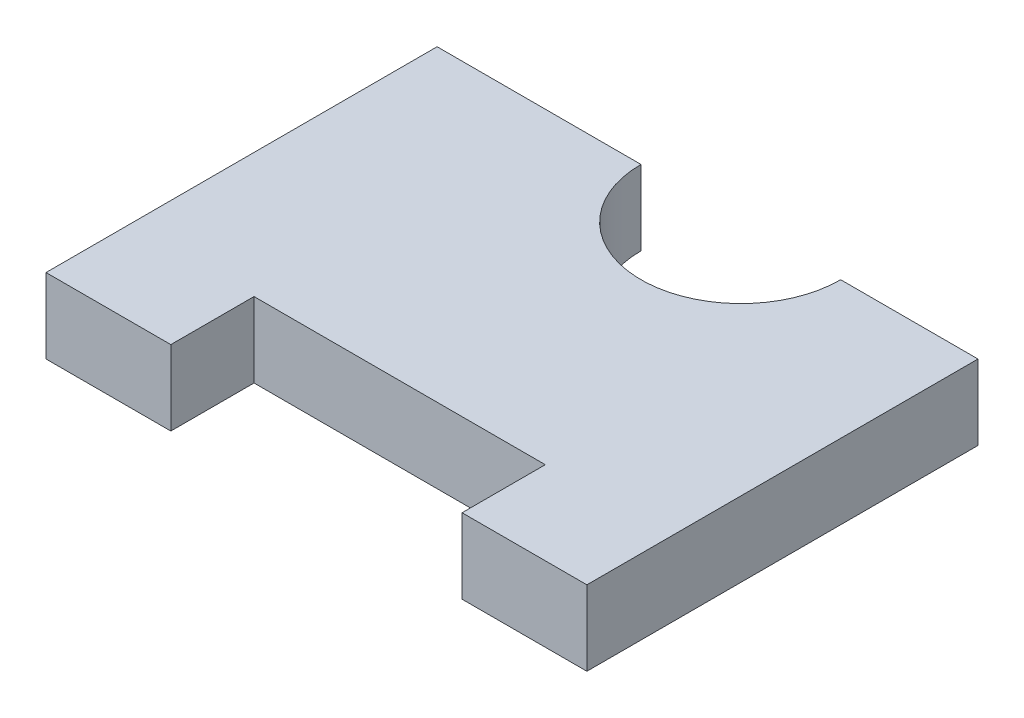
SolidWorks part; units mm, degrees
ref_plane "Front Plane" through (0, 0, 0) normal (0, 0, 1) x (1, 0, 0)
ref_plane "Top Plane" through (0, 0, 0) normal (0, 1, 0) x (1, 0, 0)
ref_plane "Right Plane" through (0, 0, 0) normal (1, 0, 0) x (0, 0, -1)
sketch "Sketch1" plane through (0, 0, 0) normal (0, 1, 0) x (1, 0, 0)
  line L0 (6.5, 5) -> (6.5, 0)
  line L1 (3.5, 0) -> (-3.5, 0)
  line L2 (-6.5, 0) -> (-6.5, 5)
  line L5 (-6.5, 5) -> (-6.5, 7.4)
  line L7 (6.5, 0) -> (6.5, -2)
  line L8 (6.5, -2) -> (3.5, -2)
  line L9 (3.5, 0) -> (3.5, -2)
  line L11 (-6.5, 0) -> (-6.5, -2)
  line L12 (-6.5, -2) -> (-3.5, -2)
  line L13 (-3.5, 0) -> (-3.5, -2)
  line L14 (-6.5, 7.4) -> (-1.6, 7.4)
  line L15 (6.5, 7.4) -> (6.5, 5)
  line L16 (3.2, 7.4) -> (6.5, 7.4)
  arc A2 (-1.6, 7.4) -> (3.2, 7.4) centre (0.8, 7.4) ccw
  point P0 (0, 0)
  dimension "D1" = 2.4
  dimension "D2" = 4.8
  dimension "D3" = 13
  dimension "D4" = 7.3
  dimension "D5" = 5
  dimension "D8" = 2
  dimension "D9" = 3
extrude "Boss-Extrude1" add sketch "Sketch1" along normal blind 1.8
ref_plane "Plane1" through (0, 0, 0) normal (0, -1, 0) x (-1, 0, 0)
